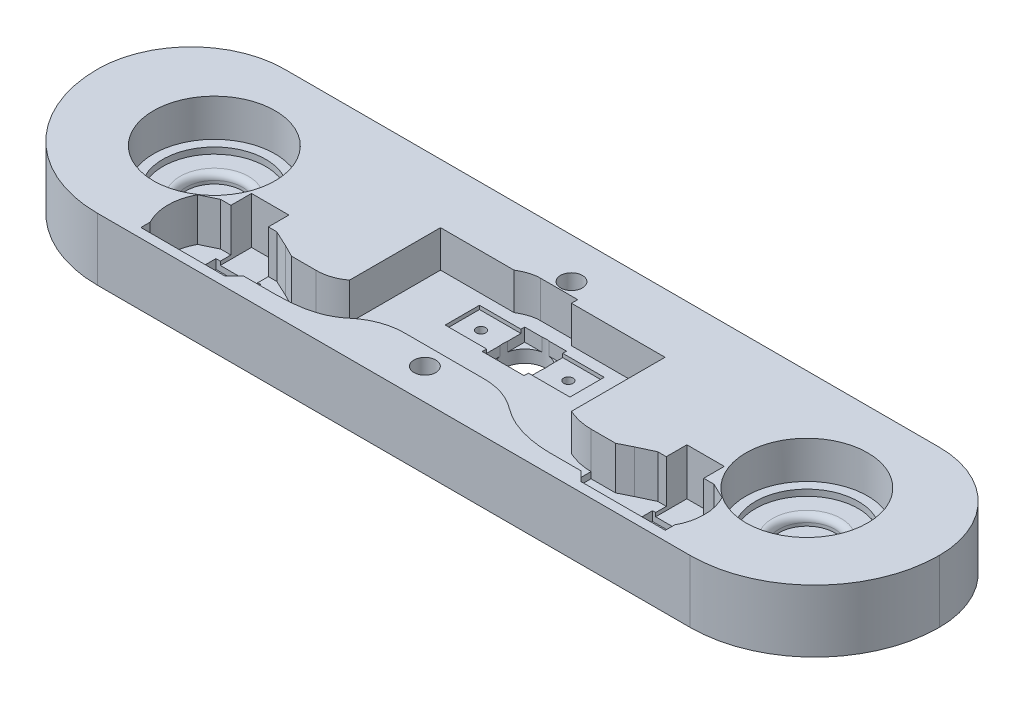
SolidWorks part; units mm, degrees
material "ABS"
ref_plane "Front Plane" through (0, 0, 0) normal (0, 0, 1) x (1, 0, 0)
ref_plane "Top Plane" through (0, 0, 0) normal (0, 1, 0) x (1, 0, 0)
ref_plane "Right Plane" through (0, 0, 0) normal (1, 0, 0) x (0, 0, -1)
sketch "Sketch1" plane through (0, 0, 0) normal (0, 1, 0) x (1, 0, 0)
  line L1 (-47.7502, 9.3769) -> (87.2498, 9.3769)
  line L2 (-47.7502, 9.3769) -> (-47.7502, -25.6231)
  line L3 (-47.7502, -25.6231) -> (87.2498, -25.6231)
  line L4 (87.2498, 9.3769) -> (87.2498, -25.6231)
  dimension "D1" = 35
  dimension "D2" = 135
extrude "Boss-Extrude1" add sketch "Sketch1" along normal blind 10
fillet "Fillet1" radius 20 2 edges at (-47.7502, 5, 25.6231) (87.2498, 5, 25.6231)
sketch "Sketch3" plane through (0, 10, 0) normal (0, 1, 0) x (1, 0, 0)
  line L1 (-47.7502, 9.3769) -> (-47.7502, -5.6231) construction
  line L2 (87.2498, 9.3769) -> (-47.7502, 9.3769) construction
  line L3 (19.7498, 5.0244) -> (19.7498, 27.1098) construction
  circle A0 centre (-27.7502, -6.8863) radius 9.75
  circle A1 centre (67.2498, -6.8863) radius 9.75
  dimension "D1" = 19.5
  dimension "D2" = 20
  dimension "D3" = 16.2632
  dimension "D4" = 67.5
sketch "Sketch5" plane through (0, 10, 0) normal (0, 1, 0) x (1, 0, 0)
  line L0 (87.2498, -5.6231) -> (87.2498, 9.3769) construction
  line L1 (87.2498, 9.3769) -> (-47.7502, 9.3769) construction
  line L2 (-27.7502, -25.6231) -> (67.2498, -25.6231) construction
  circle A0 centre (19.7498, 2.8769) radius 1.75
  circle A1 centre (19.7498, -20.6231) radius 1.75
  dimension "D1" = 3.5
  dimension "D4" = 5
  dimension "D2" = 67.5
  dimension "D3" = 6.5
extrude "Cut-Extrude3" cut sketch "Sketch5" against normal up to next
sketch "Sketch6" plane through (0, 0, 0) normal (0, -1, 0) x (1, 0, 0)
  circle A0 centre (19.7498, 20.6231) radius 3.1
  circle A1 centre (19.7498, -2.8769) radius 3.1
  dimension "D1" = 6.2
  dimension "D2" = 6.2
extrude "Cut-Extrude4" cut sketch "Sketch6" against normal blind 4
fillet "Fillet2" radius 15 2 edges at (-47.7502, 5, -9.3769) (87.2498, 5, -9.3769)
extrude "Cut-Extrude5" cut sketch "Sketch3" against normal blind 7
sketch "Sketch9" plane through (0, 3, 0) normal (0, 1, 0) x (1, 0, 0)
  circle A0 centre (-27.7502, -6.8863) radius 8.25
  circle A1 centre (-27.7502, -6.8863) radius 9.75 construction
  circle A2 centre (-27.7502, -6.8863) radius 9.75
  circle A3 centre (67.2498, -6.8863) radius 8.25
  circle A4 centre (67.2498, -6.8863) radius 9.75 construction
  circle A5 centre (67.2498, -6.8863) radius 9.75
  dimension "D1" = 16.5
  dimension "D2" = 16.5
extrude "Boss-Extrude2" add sketch "Sketch9" along normal blind 1
sketch "Sketch10" plane through (0, 3, 0) normal (0, 1, 0) x (1, 0, 0)
  circle A0 centre (-27.7502, -6.8863) radius 4.5
  circle A1 centre (67.2498, -6.8863) radius 4.5
  dimension "D1" = 9
  dimension "D2" = 9
extrude "Cut-Extrude6" cut sketch "Sketch10" against normal blind 1.5
fillet "Fillet3" radius 1 2 edges at (67.2498, 3, 11.3863) (-27.7502, 3, 11.3863)
sketch "Sketch7" plane through (0, 10, 0) normal (0, 1, 0) x (1, 0, 0)
  circle A0 centre (-15.2502, -18.6231) radius 2.5
  circle A1 centre (54.7498, -18.6231) radius 2.5
  circle A2 centre (19.7498, 2.8769) radius 1.75 construction
  dimension "D3" = 5
  dimension "D4" = 5
  dimension "D1" = 70
  dimension "D2" = 35
  dimension "D5" = 21.5
extrude "Cut-Extrude7" cut sketch "Sketch7" against normal up to next
sketch "Sketch11" plane through (0, 10, 0) normal (0, 1, 0) x (1, 0, 0)
  line L0 (19.7498, 2.8769) -> (19.7498, -20.6231) construction
  line L1 (-18.8502, -15.5231) -> (-11.6502, -15.5231)
  line L2 (-18.8502, -15.5231) -> (-18.8502, -21.7231)
  line L3 (-18.8502, -21.7231) -> (-11.6502, -21.7231)
  line L4 (-11.6502, -15.5231) -> (-11.6502, -21.7231)
  line L5 (58.3498, -21.7231) -> (51.1498, -21.7231)
  line L6 (58.3498, -15.5231) -> (58.3498, -21.7231)
  line L7 (58.3498, -15.5231) -> (51.1498, -15.5231)
  line L8 (51.1498, -15.5231) -> (51.1498, -21.7231)
  circle A0 centre (-15.2502, -18.6231) radius 2.5 construction
  dimension "D1" = 7.2
  dimension "D2" = 6.2
  dimension "D3" = 3.6
  dimension "D4" = 3.1
extrude "Cut-Extrude8" cut sketch "Sketch11" against normal offset from surface (8.4 mm away) 1.6 up to face at (-15.2502, 0, 21.1231)
sketch "Sketch12" plane through (0, 10, 0) normal (0, 1, 0) x (1, 0, 0)
  line L1 (-2.2901, -16.0231) -> (-2.2901, -22.6231)
  line L4 (-2.2901, -22.6231) -> (-22.2901, -22.6231)
  line L6 (-22.2901, -15.0231) -> (-8.2263, -15.0231)
  line L7 (19.7498, 2.8769) -> (19.7498, -20.6231) construction
  line L13 (-15.2502, -18.6231) -> (-15.2502, -20.1787) construction
  line L14 (-8.2263, -15.0231) -> (-6.2263, -16.0231)
  line L15 (-6.2263, -16.0231) -> (-2.2901, -16.0231)
  line L16 (54.7498, -18.6231) -> (54.7498, -20.1787) construction
  line L17 (45.7258, -16.0231) -> (41.7897, -16.0231)
  line L18 (47.7258, -15.0231) -> (45.7258, -16.0231)
  line L19 (61.7897, -15.0231) -> (47.7258, -15.0231)
  line L20 (41.7897, -22.6231) -> (61.7897, -22.6231)
  line L21 (41.7897, -16.0231) -> (41.7897, -22.6231)
  arc A0 (-22.2901, -15.0231) -> (-22.2901, -22.6231) centre (-15.2502, -18.8231) ccw
  circle A1 centre (-15.2502, -18.6231) radius 2.5 construction
  arc A2 (61.7897, -15.0231) -> (61.7897, -22.6231) centre (54.7498, -18.8231) cw
  dimension "D2" = 7.6
  dimension "D3" = 20
  dimension "D4" = 8
  dimension "D1" = 4
  dimension "D5" = 3.9362
  dimension "D6" = 2
  dimension "D7" = 1
extrude "Cut-Extrude9" cut sketch "Sketch12" against normal offset from surface (6.9 mm away) 1.5 up to face at (-15.2502, 1.6, 18.6231)
sketch "Sketch13" plane through (0, 10, 0) normal (0, 1, 0) x (1, 0, 0)
  line L2 (16.7498, -6.1231) -> (16.7498, -10.1231)
  line L3 (16.7498, -10.1231) -> (22.7498, -10.1231)
  line L4 (16.7498, 0.8769) -> (22.7498, 0.8769)
  line L5 (22.7498, 0.8769) -> (22.7498, -3.1231)
  line L8 (-2.2901, -16.0231) -> (-2.2901, -22.6231)
  line L9 (41.7897, -16.0231) -> (41.7897, -22.6231)
  line L10 (-2.2901, -22.6231) -> (-2.2901, -16.0231) construction
  circle A0 centre (19.7498, 2.8769) radius 1.75 construction
  circle A1 centre (19.7498, -20.6231) radius 1.75 construction
  spline S0 degree 3 poles (-2.2901, -16.0231) (1.0307, -16.0231) (5.021, -11.5533) (8.4417, -4.0824) (13.9946, 0.8769) (16.7498, 0.8769) knots 0 0 0 0 0.303661 0.653033 1 1 1 1
  spline S1 degree 3 poles (-2.2901, -22.6231) (1.4581, -22.6231) (7.0853, -21.4671) (11.3493, -13.8491) (14.3598, -6.1231) (16.7498, -6.1231) knots 0 0 0 0 0.342743 0.656632 1 1 1 1
  spline S2 degree 3 poles (22.7498, -10.1231) (24.722, -10.1231) (28.164, -15.6332) (33.1217, -21.3266) (39.0959, -22.6231) (41.7897, -22.6231) knots 0 0 0 0 0.26721 0.665148 1 1 1 1
  spline S3 degree 3 poles (22.7498, -3.1231) (25.4044, -3.1231) (30.64, -6.4865) (33.8265, -13.6596) (39.2076, -16.0231) (41.7897, -16.0231) knots 0 0 0 0 0.352459 0.667621 1 1 1 1
  dimension "D4" = 2
  dimension "D6" = 3
  dimension "D1" = 7
  dimension "D2" = 7
  dimension "D3" = 4
  dimension "D5" = 6
extrude "Cut-Extrude10" cut sketch "Sketch13" against normal offset from surface (5.9 mm away) 1 up to face at (-10.7622, 3.1, 17.8897)
sketch "Sketch14" plane through (0, 0, 0) normal (0, -1, 0) x (1, 0, 0)
  line L0 (19.7498, 20.6231) -> (19.7498, -2.8769) construction
  line L1 (72.2498, -9.3769) -> (-32.7502, -9.3769) construction
  circle A0 centre (19.7498, 4.6231) radius 3.4
  dimension "D1" = 6.8
  dimension "D2" = 14
extrude "Cut-Extrude11" cut sketch "Sketch14" against normal up to next
sketch "Sketch15" plane through (0, 4.1, 0) normal (0, 1, 0) x (1, 0, 0)
  line L1 (16.3998, -1.2731) -> (23.0998, -1.2731)
  line L2 (16.3998, -1.2731) -> (16.3998, -8.0731)
  line L3 (16.3998, -8.0731) -> (23.0998, -8.0731)
  line L4 (23.0998, -1.2731) -> (23.0998, -8.0731)
  circle A0 centre (19.7498, -4.6231) radius 3.4 construction
  dimension "D1" = 6.7
  dimension "D2" = 6.8
  dimension "D3" = 3.35
  dimension "D4" = 3.35
extrude "Cut-Extrude12" cut sketch "Sketch15" against normal offset from surface 2 and the other way up to next (5.9 mm away)
sketch "Sketch16" plane through (0, 10, 0) normal (0, 1, 0) x (1, 0, 0)
  line L1 (1.7498, -0.1231) -> (37.7498, -0.1231)
  line L2 (1.7498, -0.1231) -> (1.7498, -17.6231)
  line L3 (1.7498, -17.6231) -> (37.7498, -17.6231)
  line L4 (37.7498, -0.1231) -> (37.7498, -17.6231)
  circle A0 centre (19.7498, -4.6231) radius 3.4 construction
  dimension "D1" = 36
  dimension "D2" = 18
  dimension "D3" = 17.5
  dimension "D4" = 4.5
extrude "Cut-Extrude13" cut sketch "Sketch16" against normal up to surface (5.9 mm away) up to face at (14.7284, 4.1, 5.5459)
sketch "Sketch18" plane through (0, 10, 0) normal (0, 1, 0) x (1, 0, 0)
  line L1 (-18.1502, -15.5231) -> (-12.1502, -15.5231)
  line L2 (-18.1502, -15.5231) -> (-18.1502, -10.5231)
  line L3 (-18.1502, -10.5231) -> (-12.1502, -10.5231)
  line L4 (-12.1502, -15.5231) -> (-12.1502, -10.5231)
  line L7 (-11.6502, -15.5231) -> (-11.6502, -21.7231) construction
  line L8 (-18.8502, -15.5231) -> (-11.6502, -15.5231) construction
  line L9 (19.7498, 2.8769) -> (19.7498, -20.6231) construction
  line L10 (51.6498, -15.5231) -> (51.6498, -10.5231)
  line L11 (57.6498, -10.5231) -> (51.6498, -10.5231)
  line L12 (57.6498, -15.5231) -> (57.6498, -10.5231)
  line L13 (57.6498, -15.5231) -> (51.6498, -15.5231)
  dimension "D1" = 6
  dimension "D2" = 5
  dimension "D3" = 0.5
extrude "Cut-Extrude14" cut sketch "Sketch18" against normal blind 7.5
sketch "Sketch19" plane through (0, 10, 0) normal (0, 1, 0) x (1, 0, 0)
  line L0 (19.7498, 2.8769) -> (19.7498, -20.6231) construction
  line L1 (-22.2901, -22.6231) -> (-9.2901, -22.6231)
  line L2 (-22.2901, -22.6231) -> (-22.2901, -24.1231)
  line L3 (-22.2901, -24.1231) -> (-9.2901, -24.1231)
  line L4 (-9.2901, -22.6231) -> (-9.2901, -24.1231)
  line L5 (48.7897, -22.6231) -> (48.7897, -24.1231)
  line L6 (61.7897, -24.1231) -> (48.7897, -24.1231)
  line L7 (61.7897, -22.6231) -> (61.7897, -24.1231)
  line L8 (61.7897, -22.6231) -> (48.7897, -22.6231)
  line L10 (-22.2901, -15.0231) -> (-19.7901, -13.8231)
  line L11 (-19.7901, -13.8231) -> (-10.7901, -13.8231)
  line L12 (-10.7901, -13.8231) -> (-8.2263, -15.0231)
  line L13 (-8.2263, -15.0231) -> (-22.2901, -15.0231)
  line L14 (47.7258, -15.0231) -> (61.7897, -15.0231)
  line L15 (50.2897, -13.8231) -> (47.7258, -15.0231)
  line L16 (59.2897, -13.8231) -> (50.2897, -13.8231)
  line L17 (61.7897, -15.0231) -> (59.2897, -13.8231)
  dimension "D1" = 1.5
  dimension "D2" = 13
  dimension "D3" = 9
  dimension "D4" = 2.5
  dimension "D5" = 1.2
extrude "Cut-Extrude15" cut sketch "Sketch19" against normal up to surface (6.9 mm away) up to face at (-13.2982, 3.1, 17.3516)
chamfer "Chamfer1" distance 2 angle 45 2 edges at (48.7897, 6.55, 22.6231) (-9.2901, 6.55, 22.6231)
sketch "Sketch20" plane through (0, 3.1, 0) normal (0, 1, 0) x (1, 0, 0)
  line L0 (-20.7502, -18.6231) -> (-9.7502, -18.6231) construction
  line L1 (19.7498, 2.8769) -> (19.7498, -14.8566) construction
  line L2 (60.2498, -18.6231) -> (49.2498, -18.6231) construction
  circle A0 centre (-20.7502, -18.6231) radius 0.7
  circle A1 centre (-15.2502, -18.6231) radius 2.5 construction
  circle A2 centre (-9.7502, -18.6231) radius 0.7
  circle A3 centre (49.2498, -18.6231) radius 0.7
  circle A4 centre (60.2498, -18.6231) radius 0.7
  dimension "D1" = 5.5
  dimension "D2" = 5.5
  dimension "D3" = 1.4
  dimension "D4" = 1.4
  dimension "D5" = 0
extrude "Cut-Extrude16" cut sketch "Sketch20" against normal up to next
sketch "Sketch22" plane through (0, 4.1, 0) normal (0, 1, 0) x (1, 0, 0)
  line L1 (9.7498, -1.8731) -> (29.7498, -1.8731)
  line L2 (9.7498, -1.8731) -> (9.7498, -7.3731)
  line L3 (9.7498, -7.3731) -> (29.7498, -7.3731)
  line L4 (29.7498, -1.8731) -> (29.7498, -7.3731)
  arc A1 (19.1689, -1.2731) -> (16.3998, -4.0421) centre (19.7498, -4.6231) ccw construction
  arc A2 (19.1689, -1.2731) -> (16.3998, -4.0421) centre (19.7498, -4.6231) ccw construction
  dimension "D1" = 20
  dimension "D3" = 2.75
  dimension "D4" = 5.5
  dimension "D2" = 10
extrude "Cut-Extrude18" cut sketch "Sketch22" against normal offset from surface (0.6 mm away) 1.5 up to face at (19.7498, 2, 7.3433)
sketch "Sketch23" plane through (0, 3.5, 0) normal (0, 1, 0) x (1, 0, 0)
  circle A0 centre (12.7498, -4.6231) radius 0.75
  arc A1 (19.1689, -1.2731) -> (16.3998, -4.0421) centre (19.7498, -4.6231) ccw construction
  circle A2 centre (26.7498, -4.6231) radius 0.75
  arc A3 (23.0998, -4.0421) -> (20.3307, -1.2731) centre (19.7498, -4.6231) ccw construction
  arc A4 (16.3998, -4.0421) -> (16.3998, -5.204) centre (19.7498, -4.6231) ccw construction
  point P16 (16.3498, -4.6231)
  dimension "D3" = 1.5
  dimension "1.5" = 1.5
  dimension "D1" = 7
  dimension "D2" = 7
extrude "Cut-Extrude19" cut sketch "Sketch23" against normal up to next
fillet "Fillet4" radius 10 2 edges at (30.0999, 7.05, 17.6231) (9.0426, 7.05, 17.6231)
equation "\"D2@Sketch7\"=\"D1@Sketch7\"/2"
equation "\"D3@Sketch7\"=\"D4@Sketch7\""
equation "\"D3@Sketch11\"=\"D1@Sketch11\"/2"
equation "\"D4@Sketch11\"=\"D2@Sketch11\"/2"
equation "\"D3@Sketch15\"=\"D1@Sketch15\"/2"
equation "\"D4@Sketch15\"=\"D1@Sketch15\"/2"
equation "\"D2@Sketch21\"=\"D1@Sketch21\"/2"
equation "\"D5@Sketch21\"=\"D3@Sketch21\"/2"
equation "\"D3@Sketch22\"=\"D4@Sketch22\"/2"
